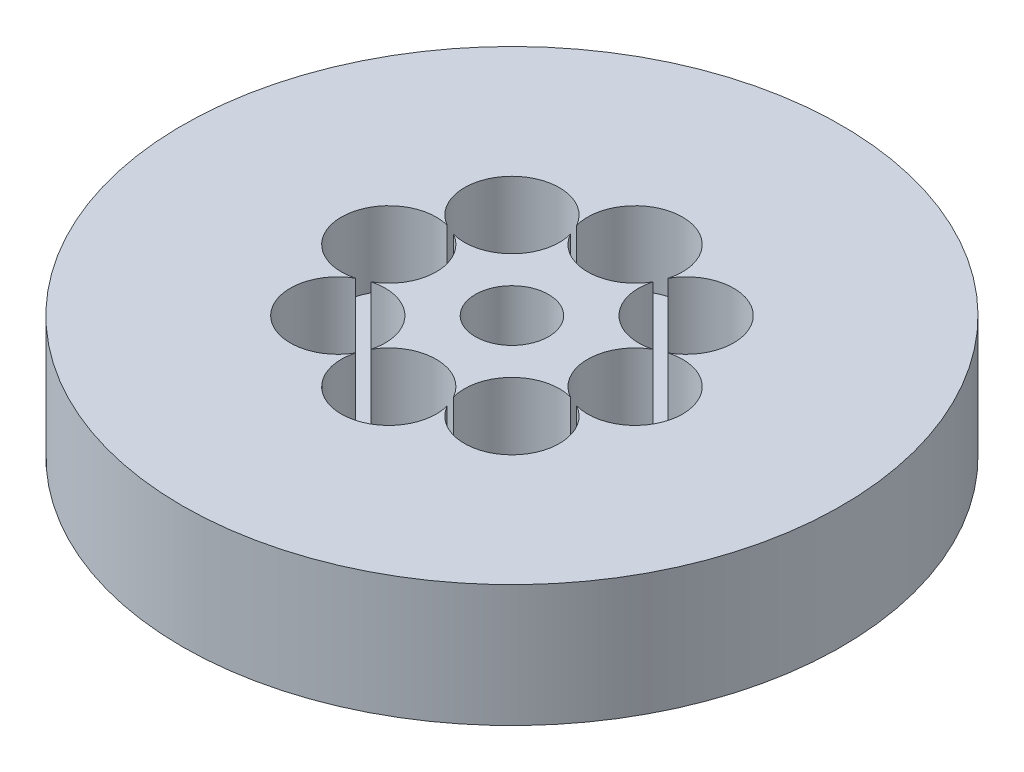
SolidWorks part; units mm, degrees
ref_plane "Front Plane" through (0, 0, 0) normal (0, 0, 1) x (1, 0, 0)
ref_plane "Top Plane" through (0, 0, 0) normal (0, 1, 0) x (1, 0, 0)
ref_plane "Right Plane" through (0, 0, 0) normal (1, 0, 0) x (0, 0, -1)
sketch "Sketch1" plane through (0, 0, 0) normal (0, 1, 0) x (1, 0, 0)
  circle A0 centre (0, 0) radius 67.5
  dimension "FLANGE_OD" = 135
extrude "Boss-Extrude1" add sketch "Sketch1" along normal blind 25
sketch "Sketch2" plane through (0, 0, 0) normal (0, 1, 0) x (1, 0, 0)
  circle A0 centre (0, 0) radius 7.5
  dimension "BORE_D" = 15
extrude "Cut-Extrude1" cut sketch "Sketch2" along normal through all
sketch "Sketch3" plane through (0, 25, 0) normal (0, 1, 0) x (1, 0, 0)
  circle A0 centre (0, 0) radius 25.2237 construction
  circle A1 centre (-25.2237, 0) radius 9.7266
  dimension "BOLT_D" = 19.4533
  dimension "BOLT_PCD" = 50.4474
extrude "Cut-Extrude2" cut sketch "Sketch3" against normal blind 15.2307
pattern_circular "CirPattern1" count 8 over 360 about axis through (0, 0, 0) along (0, 1, 0) of "Cut-Extrude2"
